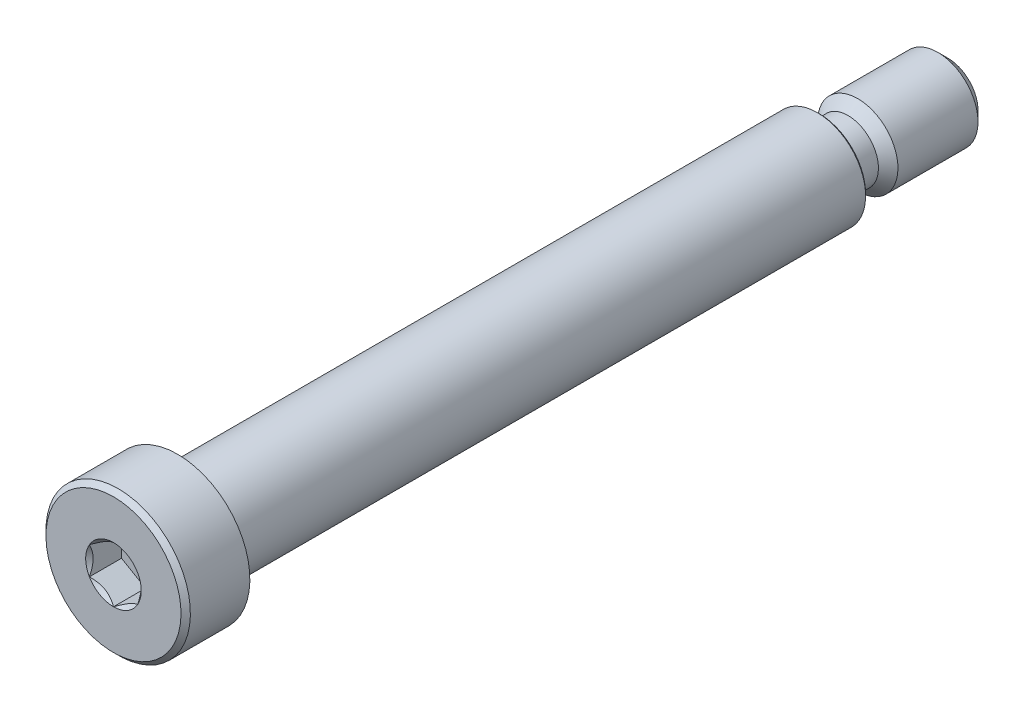
SolidWorks part; units mm, degrees
material "Plain Carbon Steel"
ref_plane "Front" through (0, 0, 0) normal (0, 0, 1) x (1, 0, 0)
ref_plane "Top" through (0, 0, 0) normal (0, 1, 0) x (1, 0, 0)
ref_plane "Right" through (0, 0, 0) normal (1, 0, 0) x (0, 0, -1)
sketch "Sketch1" plane through (0, 0, 0) normal (1, 0, 0) x (0, 0, -1)
  line L0 (0, 7.1437) -> (6.35, 7.1437)
  line L1 (6.35, 7.1437) -> (6.35, 4.7625)
  line L2 (6.35, 4.7625) -> (69.85, 4.7625)
  line L3 (69.85, 4.7625) -> (69.85, 3.9751)
  line L4 (69.85, 3.9751) -> (82.55, 3.9751)
  line L5 (82.55, 3.9751) -> (82.55, 0)
  line L6 (82.55, 0) -> (0, 0)
  line L7 (0, 0) -> (0, 7.1437)
  line L8 (0, 7.1437) -> (0, -7.1438) construction
  line L9 (82.55, 3.9751) -> (82.55, -3.9751) construction
  line L10 (69.85, 4.7625) -> (69.85, -4.7625) construction
  line L11 (82.55, -3.9751) -> (80.8722, -3.9751) construction
  line L12 (38.1, 0) -> (38.1, 4.7625) construction
  point P8 (80.4333, -3.9751)
  point P12 (69.85, 0)
  point P17 (12.7, 4.7625)
  point P18 (38.1, 0)
  point P19 (38.1, 4.7625)
  point P20 (63.5, 4.7625)
  point P21 (63.5, -4.7625)
  point P22 (12.7, -4.7625)
  dimension "Head Dia" = 14.2875
  dimension "Head Ht" = 6.35
  dimension "Thread Lg" = 12.7
  dimension "Thread Dia" = 7.9502
  dimension "Shoulder Dia" = 9.525
  dimension "Shoulder Lg" = 63.5
  dimension "D1" = 2.1167
  dimension "D2" = 1.6778
  dimension "D3" = 31.75
  dimension "D4" = 6.35
revolve "Revolve1" add sketch "Sketch1" angle 360 mid plane about L6
ref_plane "Plane1" through (0, 0, -82.55) normal (0, 0, 1) x (1, 0, 0)
sketch "Sketch3" plane through (0, 0, -82.55) normal (0, 0, 1) x (1, 0, 0)
  circle A0 centre (0, 0) radius 3.9751
sketch "Sketch5" plane through (0, 0, 0) normal (1, 0, 0) x (0, 0, -1)
  line L0 (69.85, 4.7625) -> (74.422, 4.7625)
  line L1 (74.422, 4.7625) -> (72.6694, 3.0099)
  line L2 (72.6694, 3.0099) -> (70.8152, 3.0099)
  line L3 (69.85, 4.7625) -> (69.85, 3.9751)
  line L5 (69.85, 3.9751) -> (82.55, 3.9751) construction
  line L6 (82.55, 0) -> (72.6694, 0) construction
  line L7 (77.6097, 0) -> (77.6097, -3.9751) construction
  arc A0 (69.85, 3.9751) -> (70.8152, 3.0099) centre (70.8152, 3.9751) ccw
  dimension "D1" = 45
  dimension "CADB" = 2.8194
  dimension "CADA" = 6.0198
revolve "Cut-Revolve1" cut sketch "Sketch5" angle 360 mid plane about L6
chamfer "Chamfer1" distance 0.9938 angle 45 1 edges at (0, 3.9751, -82.55)
chamfer "Chamfer2" distance 0.4643 angle 45 1 edges at (0, 7.1437, 0)
chamfer "Chamfer3" distance 0.2032 angle 45 1 edges at (0, 4.7625, -69.85)
sketch "Sketch10" plane through (0, 0, 0) normal (1, 0, 0) x (0, 0, -1)
  line L0 (0.4643, 0) -> (5.8857, 0) construction
  line L1 (0.4643, -7.1437) -> (0.4643, 7.1437) construction
  line L3 (0.4643, 0) -> (0, 0) construction
  line L4 (5.8857, 0) -> (6.35, 0) construction
  line L5 (6.35, -7.1437) -> (6.35, 7.1437) construction
  point P6 (3.175, 0)
  dimension "D1" = 5.4213
ref_plane "Plane2" through (0, 0, -3.175) normal (0, 0, 1) x (1, 0, 0)
sketch "Sketch11" plane through (0, 0, -3.175) normal (0, 0, 1) x (1, 0, 0)
  line L0 (0, 6.7723) -> (0, 7.1437) construction
  line L1 (0, 6.7723) -> (0.2145, 7.1437)
  line L2 (0, 6.7723) -> (-0.2145, 7.1437)
  line L3 (-0.2145, 7.1437) -> (0.2145, 7.1437)
  line L4 (0, 0) -> (-0.2145, 7.1437) construction
  line L5 (0.2145, 7.1437) -> (0, 0) construction
  circle A1 centre (0, 0) radius 7.1437 construction
  circle A2 centre (0, 0) radius 6.7723 construction
  circle A3 centre (0, 0) radius 6.6794 construction
  point P3 (0, 0.0018)
  point P8 (2.3908, 0.7309)
  dimension "D1" = 0.3715
  dimension "D2" = 3.439
extrude "Cut-Extrude5" [suppressed] cut sketch "Sketch11" against normal mid plane 5.1502
pattern_circular "CirPattern1" [suppressed] count 99 over 360 of bodies 119
sketch "Sketch8" plane through (0, 0, 0) normal (0, 0, 1) x (1, 0, 0)
  line L1 (2.3813, 1.3748) -> (0, 2.7496)
  line L2 (0, 2.7496) -> (-2.3812, 1.3748)
  line L3 (-2.3812, 1.3748) -> (-2.3812, -1.3748)
  line L4 (-2.3812, -1.3748) -> (0, -2.7496)
  line L5 (0, -2.7496) -> (2.3813, -1.3748)
  line L6 (2.3813, -1.3748) -> (2.3813, 1.3748)
  circle A0 centre (0, 0) radius 2.3812 construction
  dimension "Hex" = 4.7625
extrude "Cut-Extrude2" cut sketch "Sketch8" against normal blind 3.175
sketch "Sketch9" plane through (0, 0, 0) normal (0, 0, 1) x (1, 0, 0)
  circle A0 centre (0, 0) radius 2.7496
extrude "Cut-Extrude4" cut sketch "Sketch9" against normal blind 3.175 draft 45
sketch "Front Sketch" plane through (0, 0, 0) normal (0, 0, 1) x (1, 0, 0)
  line L0 (2.3813, -1.3748) -> (2.3813, 1.3748) construction
  line L1 (-2.3812, 1.3748) -> (-2.3812, -1.3748) construction
  circle A0 centre (0, 0) radius 7.1437 construction
  point P4 (-2.3812, 0)
  point P5 (2.3813, 0)
  point P6 (7.1437, 0)
  point P9 (-7.1437, 0)
ref_plane "Contact Plane 1" through (0, 0, -6.35) normal (0, 0, -1) x (-1, 0, 0)
ref_axis "Center Axis 1" through (0, 0, -82.55) along (0, 0, 1)
curve "Helix/Spiral1" pitch 1.4111 height 14.1111 turns 10
sketch "Sketch4" plane through (0, 0, 0) normal (1, 0, 0) x (0, 0, -1)
  line L0 (82.4618, 4.1279) -> (83.8729, 4.1279) construction
  line L1 (83.8729, 4.1279) -> (83.1674, 2.9058) construction
  line L3 (83.1674, 2.9058) -> (82.4618, 4.1279) construction
  line L4 (82.5059, 4.0515) -> (83.8288, 4.0515) construction
  line L5 (82.55, 3.9751) -> (83.7847, 3.9751) construction
  line L6 (83.0792, 3.0586) -> (83.2556, 3.0586) construction
  line L7 (83.1674, 3.0586) -> (83.1674, 2.9058) construction
  line L8 (83.1674, 4.1279) -> (83.1674, 3.9751) construction
  line L9 (82.5059, 4.0515) -> (83.8288, 4.0515)
  line L10 (83.8288, 4.0515) -> (83.2556, 3.0586)
  line L11 (83.2556, 3.0586) -> (83.0792, 3.0586)
  line L12 (83.0792, 3.0586) -> (82.5059, 4.0515)
  point P14 (83.1674, 4.0515)
  point P15 (83.1674, 4.1279)
  dimension "D1" = 1.4111
  dimension "D2" = 0.1764
sweep "Cut-Sweep1" [suppressed] cut profiles "Sketch4" path "Helix/Spiral1"
sketch "Sketch12" plane through (0, 0, 0) normal (1, 0, 0) x (0, 0, -1)
  line L1 (69.85, 4.5593) -> (69.6468, 4.7625)
  line L2 (69.6468, 4.7625) -> (6.35, 4.7625)
  line L3 (6.35, 4.7625) -> (6.35, 0)
  line L4 (6.35, -7.1437) -> (6.35, 7.1437) construction
  line L5 (6.35, 0) -> (69.85, 0)
  line L6 (69.85, 4.5593) -> (69.85, 3.9751)
  line L7 (72.6694, 3.0099) -> (70.8152, 3.0099) construction
  line L8 (72.6694, 3.0099) -> (70.8152, 3.0099)
  line L9 (72.6694, 3.0099) -> (72.6694, 0)
  line L10 (72.6694, 0) -> (69.85, 0)
  arc A0 (69.85, 3.9751) -> (70.8152, 3.0099) centre (70.8152, 3.9751) ccw construction
  arc A1 (69.85, 3.9751) -> (70.8152, 3.0099) centre (70.8152, 3.9751) ccw
revolve "Revolve2" add sketch "Sketch12" angle 360 about L5
equation "\"D3@Helix/Spiral1\" = \"Thread Lg@Sketch1\" + \"D4@Helix/Spiral1\""
equation "\"D1@Chamfer1\" = \"Thread Dia@Sketch1\" * .125"
equation "\"D1@Cut-Extrude2\"= \"Head Ht@Sketch1\" * .5"
equation "\"D1@Cut-Extrude4\" = \"D1@Cut-Extrude2\""
equation "\"D1@Chamfer2\" = \"Head Dia@Sketch1\" * .0325"
equation "\"D1@Sketch1\"=\"D4@Helix/Spiral1\"*1.5"
equation "\"D1@Sketch11\"=\"D1@Chamfer2\"*.8"
equation "\"D1@Cut-Extrude5\"=\"D1@Sketch10\"*.95"
equation "\"D1@CirPattern1\"=(360/\"D2@Sketch11\")-6"
equation "\"D3@Sketch1\"=\"Shoulder Lg@Sketch1\"/2"
equation "\"D4@Sketch1\"=\"D3@Sketch1\"*.2"
equation "\"D1@Sketch4\"=\"D4@Helix/Spiral1\""
equation "\"D2@Sketch4\"=\"D1@Sketch4\"/8"
